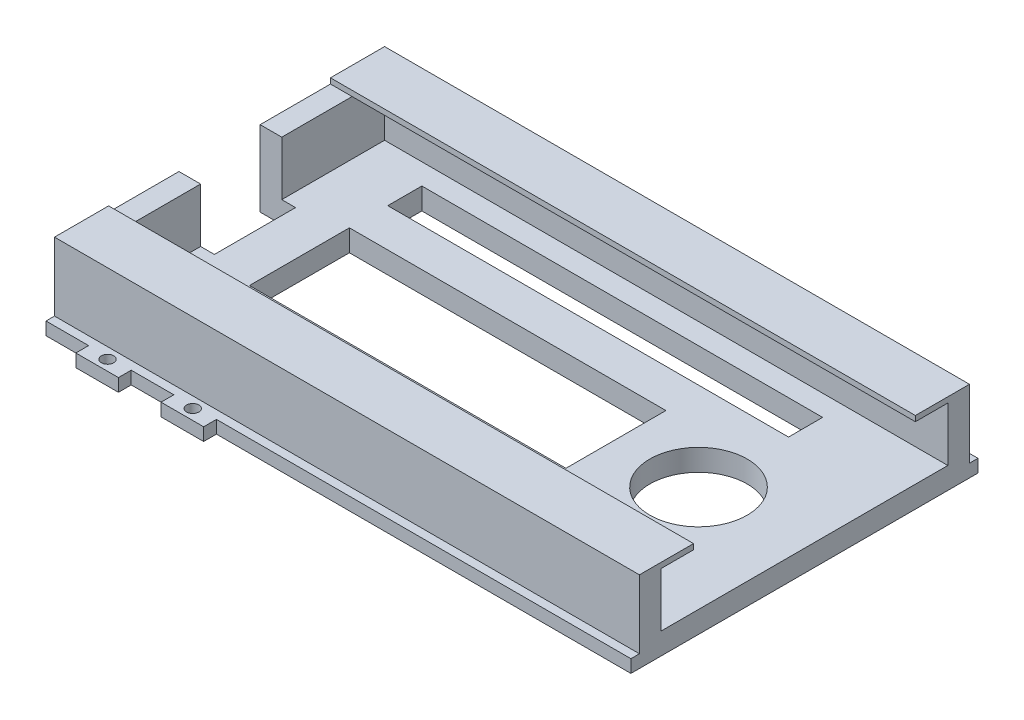
SolidWorks part; units mm, degrees
ref_plane "Front Plane" through (0, 0, 0) normal (0, 0, 1) x (1, 0, 0)
ref_plane "Top Plane" through (0, 0, 0) normal (0, 1, 0) x (1, 0, 0)
ref_plane "Right Plane" through (0, 0, 0) normal (1, 0, 0) x (0, 0, -1)
sketch "Sketch1" plane through (0, 0, 0) normal (0, 1, 0) x (1, 0, 0)
  line L1 (68.6435, -38.735) -> (-68.6435, -38.735)
  line L2 (68.6435, -38.735) -> (68.6435, 38.735)
  line L3 (68.6435, 38.735) -> (-68.6435, 38.735)
  line L4 (-68.6435, -38.735) -> (-68.6435, 38.735)
  line L5 (0, 38.735) -> (0, -38.735) construction
  line L6 (68.6435, 0) -> (-68.6435, 0) construction
  point P0 (0, 0)
extrude "Boss-Extrude1" add sketch "Sketch1" along normal blind 17.78
sketch "Sketch2" plane through (0, 17.78, 0) normal (0, 1, 0) x (1, 0, 0)
  line L0 (68.6435, -38.735) -> (68.6435, 38.735) construction
  line L1 (-63.5635, 33.655) -> (68.6435, 33.655)
  line L2 (-63.5635, 33.655) -> (-63.5635, -33.655)
  line L3 (-63.5635, -33.655) -> (68.6435, -33.655)
  line L4 (68.6435, 33.655) -> (68.6435, -33.655)
  line L5 (-68.6435, 38.735) -> (-68.6435, -38.735) construction
  line L6 (68.6435, 38.735) -> (-68.6435, 38.735) construction
  line L7 (-68.6435, -38.735) -> (68.6435, -38.735) construction
  dimension "D1" = 0
  dimension "D2" = 5.08
  dimension "D3" = 5.08
  dimension "D4" = 5.08
extrude "Cut-Extrude1" cut sketch "Sketch2" against normal blind 12.7
sketch "Sketch4" plane through (0, 5.08, 0) normal (0, 1, 0) x (1, 0, 0)
  line L0 (-63.5635, 33.655) -> (-63.5635, -33.655) construction
  circle A0 centre (43.7769, 0) radius 11.43
  dimension "D1" = 107.3404
extrude "Cut-Extrude2" cut sketch "Sketch4" against normal through all contours A0
sketch "Sketch5" plane through (0, 17.78, 0) normal (0, 1, 0) x (1, 0, 0)
  line L0 (68.6435, -33.655) -> (68.6435, 33.655) construction
  line L1 (-68.6435, 38.735) -> (68.6435, 38.735)
  line L2 (-68.6435, 38.735) -> (-68.6435, 26.035)
  line L3 (-68.6435, 26.035) -> (68.6435, 26.035)
  line L4 (68.6435, 38.735) -> (68.6435, 26.035)
  line L5 (-68.6435, 38.735) -> (-68.6435, -38.735) construction
  line L6 (68.6435, -38.735) -> (-68.6435, -38.735)
  line L7 (68.6435, -38.735) -> (68.6435, -26.035)
  line L8 (68.6435, -26.035) -> (-68.6435, -26.035)
  line L9 (-68.6435, -38.735) -> (-68.6435, -26.035)
  dimension "D1" = 12.7
  dimension "D2" = 12.7
extrude "Boss-Extrude2" add sketch "Sketch5" along normal blind 1.27
sketch "Sketch6" plane through (0, 17.78, 0) normal (0, 1, 0) x (1, 0, 0)
  line L0 (-68.6435, 26.035) -> (-68.6435, -26.035) construction
  line L1 (-68.6435, 9.525) -> (-60.3292, 9.525)
  line L2 (-68.6435, 9.525) -> (-68.6435, -9.525)
  line L3 (-68.6435, -9.525) -> (-60.3292, -9.525)
  line L4 (-60.3292, 9.525) -> (-60.3292, -9.525)
  line L5 (68.6435, 38.735) -> (-68.6435, 38.735) construction
  line L6 (-68.6435, -38.735) -> (68.6435, -38.735) construction
  dimension "D1" = 29.21
  dimension "D2" = 29.21
extrude "Cut-Extrude3" cut sketch "Sketch6" against normal through all
sketch "Sketch9" plane through (0, 0, 0) normal (0, -1, 0) x (-1, 0, 0)
  line L0 (68.6435, -9.525) -> (68.6435, -38.735) construction
  line L1 (-68.6435, -38.735) -> (68.6435, -38.735)
  line L2 (-68.6435, -38.735) -> (-68.6435, -40.735)
  line L3 (-68.6435, -40.735) -> (68.6435, -40.735)
  line L4 (68.6435, -38.735) -> (68.6435, -40.735)
  line L5 (68.6435, 38.735) -> (-68.6435, 38.735)
  line L6 (68.6435, 38.735) -> (68.6435, 40.735)
  line L7 (68.6435, 40.735) -> (-68.6435, 40.735)
  line L8 (-68.6435, 38.735) -> (-68.6435, 40.735)
  line L9 (58.6435, -40.735) -> (48.6435, -40.735)
  line L10 (58.6435, -40.735) -> (58.6435, -43.735)
  line L11 (58.6435, -43.735) -> (48.6435, -43.735)
  line L12 (48.6435, -40.735) -> (48.6435, -43.735)
  line L13 (58.6435, 40.735) -> (48.6435, 40.735)
  line L14 (58.6435, 40.735) -> (58.6435, 43.735)
  line L15 (58.6435, 43.735) -> (48.6435, 43.735)
  line L16 (48.6435, 40.735) -> (48.6435, 43.735)
  line L17 (38.6435, -40.735) -> (28.6435, -40.735)
  line L18 (38.6435, -40.735) -> (38.6435, -43.735)
  line L19 (38.6435, -43.735) -> (28.6435, -43.735)
  line L20 (28.6435, -40.735) -> (28.6435, -43.735)
  line L21 (38.6435, 40.735) -> (28.6435, 40.735)
  line L22 (38.6435, 40.735) -> (38.6435, 43.735)
  line L23 (38.6435, 43.735) -> (28.6435, 43.735)
  line L24 (28.6435, 40.735) -> (28.6435, 43.735)
  dimension "D1" = 2
  dimension "D2" = 2
  dimension "D3" = 10
  dimension "D4" = 10
  dimension "D5" = 10
  dimension "D6" = 10
  dimension "D7" = 10
  dimension "D8" = 10
  dimension "D9" = 10
  dimension "D10" = 10
  dimension "D11" = 3
  dimension "D12" = 3
  dimension "D13" = 3
  dimension "D14" = 3
extrude "Boss-Extrude4" add sketch "Sketch9" against normal blind 3 contours L23 L24 L21 L22 | L7 L8 L5 L6 | L15 L16 L13 L14 | L19 L20 L17 L18 | L11 L12 L9 L10 | L1 L4 L3 L2
sketch "Sketch10" plane through (0, 0, 0) normal (0, -1, 0) x (-1, 0, 0)
  line L0 (58.6435, 43.735) -> (48.6435, 43.735) construction
  line L1 (38.6435, 43.735) -> (28.6435, 43.735) construction
  line L2 (38.6435, -43.735) -> (28.6435, -43.735) construction
  line L3 (58.6435, -43.735) -> (48.6435, -43.735) construction
  line L4 (58.6435, -40.735) -> (58.6435, -43.735) construction
  line L5 (38.6435, -40.735) -> (38.6435, -43.735) construction
  line L6 (38.6435, 40.735) -> (38.6435, 43.735) construction
  line L7 (58.6435, 40.735) -> (58.6435, 43.735) construction
  circle A0 centre (33.6435, -41.295) radius 1.44
  circle A1 centre (53.6435, -41.295) radius 1.44
  circle A2 centre (53.6435, 41.295) radius 1.44
  circle A3 centre (33.6435, 41.295) radius 1.44
  dimension "D1" = 2.44
  dimension "D2" = 2.44
  dimension "D4" = 2.44
  dimension "D5" = 5
  dimension "D6" = 5
  dimension "D7" = 5
  dimension "D8" = 5
  dimension "D3" = 2.44
extrude "Cut-Extrude4" cut sketch "Sketch10" against normal through all
sketch "Sketch11" plane through (0, 0, 0) normal (0, -1, 0) x (1, 0, 0)
  line L0 (-38.6435, 40.735) -> (-48.6435, 40.735) construction
  line L1 (24.3921, 11.735) -> (-49.8976, 11.735)
  line L2 (24.3921, 11.735) -> (24.3921, -11.735)
  line L3 (24.3921, -11.735) -> (-49.8976, -11.735)
  line L4 (-49.8976, 11.735) -> (-49.8976, -11.735)
  line L5 (-49.8976, 20.735) -> (44.172, 20.735)
  line L6 (-49.8976, 20.735) -> (-49.8976, 28.735)
  line L7 (-49.8976, 28.735) -> (44.172, 28.735)
  line L8 (44.172, 20.735) -> (44.172, 28.735)
  line L9 (-49.8976, -28.735) -> (44.172, -28.735)
  line L10 (-49.8976, -28.735) -> (-49.8976, -20.735)
  line L11 (-49.8976, -20.735) -> (44.172, -20.735)
  line L12 (44.172, -28.735) -> (44.172, -20.735)
  line L13 (-28.6435, -40.735) -> (68.6435, -40.735) construction
  line L14 (68.6435, 40.735) -> (-28.6435, 40.735) construction
  point P16 (-2.8628, 28.735)
  dimension "D1" = 29
  dimension "D2" = 29
  dimension "D3" = 12
  dimension "D4" = 20
  dimension "D5" = 12
  dimension "D6" = 20
extrude "Cut-Extrude5" cut sketch "Sketch11" against normal blind 10
